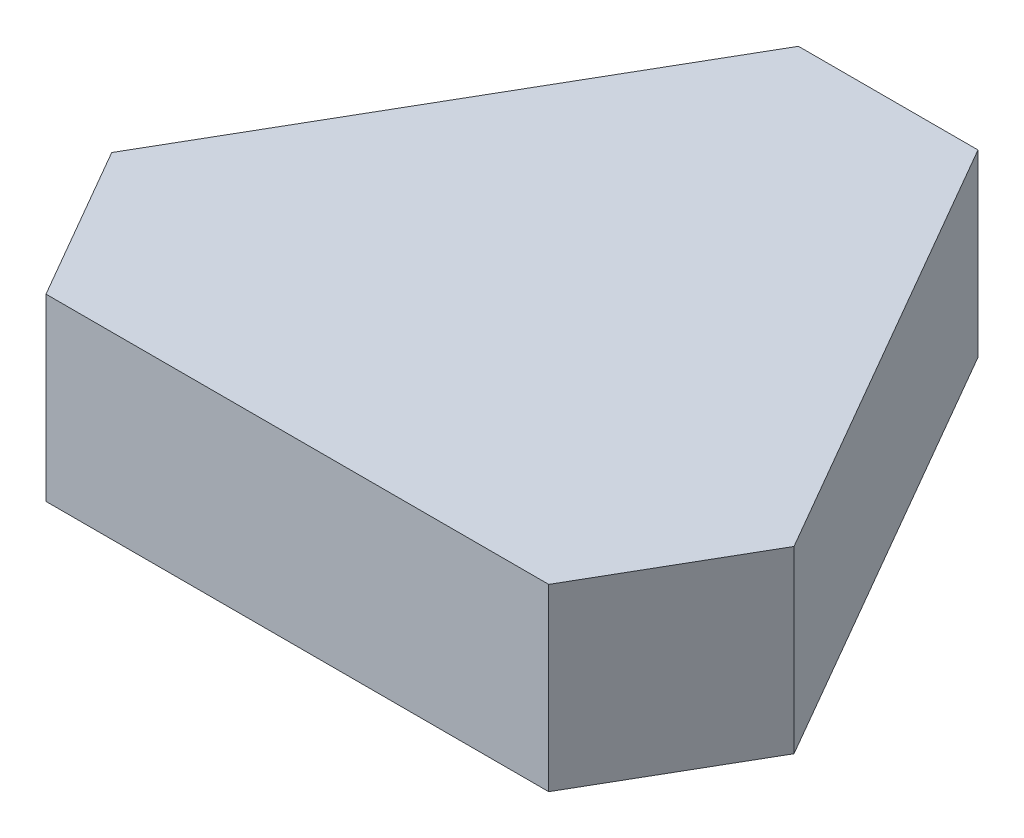
SolidWorks part; units mm, degrees
ref_plane "Front Plane" through (0, 0, 0) normal (0, 0, 1) x (1, 0, 0)
ref_plane "Top Plane" through (0, 0, 0) normal (0, 1, 0) x (1, 0, 0)
ref_plane "Right Plane" through (0, 0, 0) normal (1, 0, 0) x (0, 0, -1)
sketch "Schizzo1" plane through (0, 0, 0) normal (0, 1, 0) x (1, 0, 0)
  line L0 (-24, -13.8564) -> (0, 27.7128)
  line L1 (0, 27.7128) -> (24, -13.8564)
  line L2 (24, -13.8564) -> (-24, -13.8564)
  line L3 (0, 27.7128) -> (0, -13.8564) construction
  line L5 (-24, -13.8564) -> (12, 6.9282) construction
  point P2 (0, 0)
  point P4 (0, -13.8564)
  point P6 (0, 0)
  point P8 (0, 0)
  point P9 (0, 0)
  dimension "D1" = 48
extrude "Estrusione-Estrusione1" add sketch "Schizzo1" along normal mid plane 10
sketch "Schizzo2" plane through (0, 5, 0) normal (0, 1, 0) x (1, 0, 0)
  line L0 (14, -13.8564) -> (19, -5.1962)
  line L1 (-24, -13.8564) -> (24, -13.8564) construction
  line L2 (24, -13.8564) -> (0, 27.7128) construction
  line L3 (0, 0) -> (16.5, -9.5263) construction
  line L4 (16.5, -9.5263) -> (24, -13.8564) construction
  line L5 (14, -13.8564) -> (24, -13.8564)
  line L6 (24, -13.8564) -> (19, -5.1962)
  dimension "D1" = 10
extrude "Taglio-Estrusione1" cut sketch "Schizzo2" against normal up to surface (10 mm away) up to face at (0, -5, 0)
ref_axis "Assi1" through (0, -5.5, 0) along (0, 1, 0)
pattern_circular "RipetizioneCircolare1" count 3 over 360 about axis through (0, -5.5, 0) along (0, 1, 0) of "Taglio-Estrusione1"
